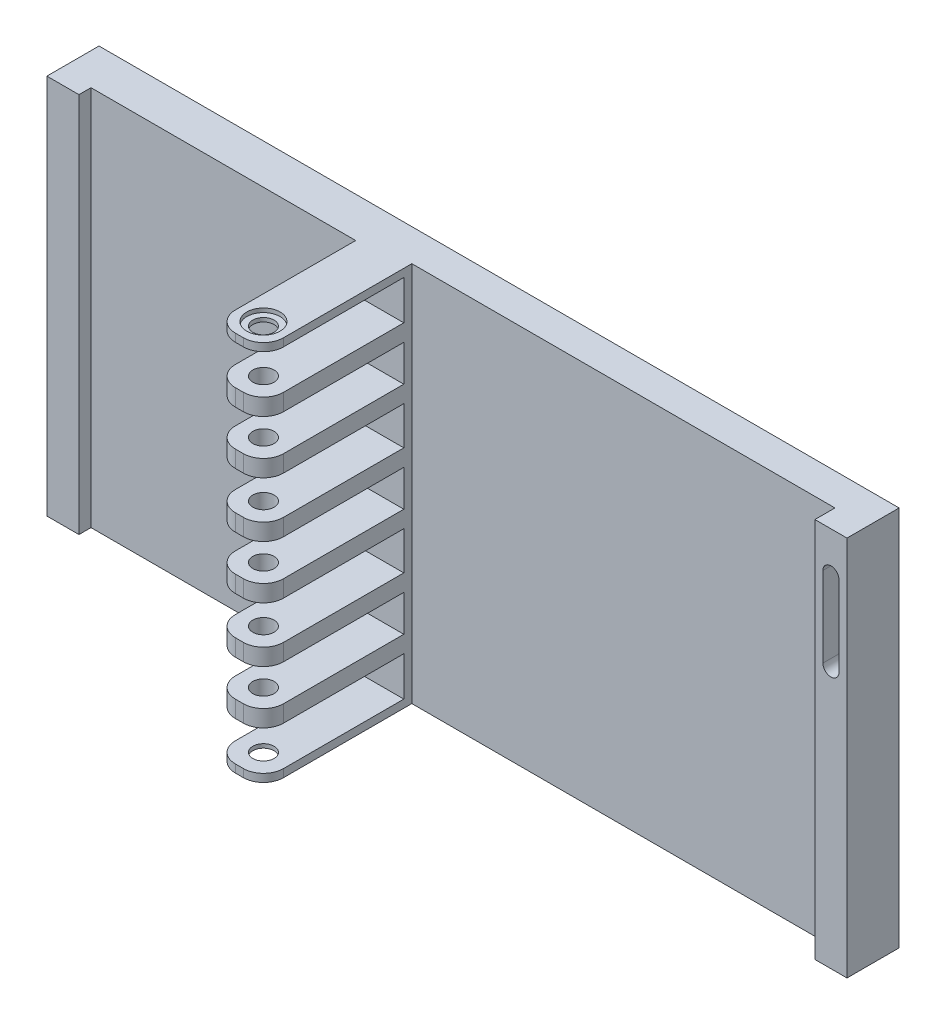
SolidWorks part; units mm, degrees
ref_plane "Front Plane" through (0, 0, 0) normal (1, 0, 0) x (0, 1, 0)
ref_plane "Top Plane" through (0, 0, 0) normal (0, 0, 1) x (0, 1, 0)
ref_plane "Right Plane" through (0, 0, 0) normal (0, 1, 0) x (-1, 0, 0)
sketch "Sketch1" plane through (0, 0, 0) normal (0, 0, 1) x (0, 1, 0)
  line L1 (0, 0) -> (-95, 0)
  line L2 (0, 0) -> (0, 12)
  line L3 (0, 12) -> (-95, 12)
  line L4 (-95, 0) -> (-95, 12)
extrude "Boss-Extrude1" add sketch "Sketch1" along normal blind 10 contours L3 L4 L1 L2
sketch "Sketch3" plane through (0, 0, 10) normal (0, 0, 1) x (1, 0, 0)
  line L0 (0, 0) -> (0, -95) construction
  line L1 (-12, 0) -> (0, 0)
  line L2 (-12, 0) -> (-12, -1.975)
  line L3 (-12, -1.975) -> (0, -1.975)
  line L4 (0, 0) -> (0, -1.975)
  line L6 (-12, -1.975) -> (0, -1.975) construction
  line L8 (-12, -11.775) -> (0, -11.775) construction
  line L10 (-12, -11.775) -> (0, -11.775)
  line L11 (-12, -11.775) -> (-12, -15.975)
  line L12 (-12, -15.975) -> (0, -15.975)
  line L13 (0, -11.775) -> (0, -15.975)
  line L14 (-12, -15.975) -> (0, -15.975) construction
  line L16 (-12, -25.025) -> (0, -25.025) construction
  line L18 (0, -25.025) -> (-12, -25.025)
  line L19 (0, -25.025) -> (0, -29.225)
  line L20 (0, -29.225) -> (-12, -29.225)
  line L21 (-12, -25.025) -> (-12, -29.225)
  line L23 (-12, -29.225) -> (0, -29.225) construction
  line L25 (-12, -38.775) -> (0, -38.775) construction
  line L27 (-12, -38.775) -> (0, -38.775)
  line L28 (-12, -38.775) -> (-12, -42.975)
  line L29 (-12, -42.975) -> (0, -42.975)
  line L30 (0, -38.775) -> (0, -42.975)
  dimension "D1" = 1.975
  dimension "D2" = 9.8
  dimension "D3" = 4.2
  dimension "D4" = 9.05
  dimension "D5" = 4.2
  dimension "D6" = 9.55
  dimension "D7" = 4.2
extrude "Boss-Extrude2" add sketch "Sketch3" along normal blind 35
fillet "Fillet1" radius 5 8 edges at (-12, -0.9875, 45) (0, -0.9875, 45) (-12, -13.875, 45) (0, -13.875, 45) (-12, -40.875, 45) (-12, -27.125, 45) (0, -27.125, 45) (0, -40.875, 45)
ref_plane "Plane1" through (0, -47.5, 0) normal (0, 1, 0) x (1, 0, 0)
mirror "Mirror1" about plane through (0, -47.5, 0) normal (0, 1, 0) of "Fillet1", "Boss-Extrude2"
sketch "Sketch5" plane through (0, 0, 0) normal (0, 1, 0) x (-1, 0, 0)
  line L0 (5, 45) -> (7, 45) construction
  line L1 (6, 45) -> (0, 45)
  line L2 (6, 45) -> (6, 39)
  line L3 (6, 39) -> (0, 39)
  line L4 (0, 45) -> (0, 39)
  circle A0 centre (6, 39) radius 2.65
  dimension "D1" = 6
extrude "Cut-Extrude1" cut sketch "Sketch5" against normal through all contours A0
sketch "Sketch7" plane through (0, 0, 0) normal (0, 1, 0) x (-1, 0, 0)
  line L0 (5, 45) -> (7, 45) construction
  line L1 (6, 45) -> (0, 45)
  line L2 (6, 45) -> (6, 39)
  line L3 (6, 39) -> (0, 39)
  line L4 (0, 45) -> (0, 39)
  line L5 (0, 40) -> (0, 0) construction
  circle A0 centre (6, 39) radius 4.15
  circle M6 centre (6, 39) radius 2.65
  dimension "D1" = 6
extrude "Cut-Extrude2" cut sketch "Sketch7" against normal blind 1 contours L3 A0 L2 M6 | L2 A0 L3 M6 region at (-8.8515, 0, 41.8515) region at (-3.8004, 0, 41.1996)
mirror "Mirror2" about plane through (0, -47.5, 0) normal (0, 1, 0) of "Cut-Extrude2"
sketch "Sketch8" plane through (0, 0, 0) normal (0, 0, -1) x (1, 0, 0)
  line L0 (0, 95) -> (-12, 95) construction
  line L1 (-6, 95) -> (-86, 95)
  line L2 (-6, 95) -> (-6, 0)
  line L3 (-6, 0) -> (-86, 0)
  line L4 (-86, 95) -> (-86, 0)
  line L5 (-6, 95) -> (113.5, 95)
  line L6 (-6, 95) -> (-6, 0)
  line L7 (-6, 0) -> (113.5, 0)
  line L8 (113.5, 95) -> (113.5, 0)
  line L9 (0, 0) -> (-12, 0) construction
  line M2 (0, 0) -> (0, 95)
  line M4 (-12, 95) -> (-12, 0)
  dimension "D1" = 119.5
  dimension "D2" = 80
extrude "Boss-Extrude3" add sketch "Sketch8" against normal blind 8 contours L1 L4 L3 M4 | L8 L5 L7 M2 region at (-49, -47.5, 0) region at (56.75, -47.5, 0)
sketch "Sketch9" plane through (0, 0, 8) normal (0, 0, 1) x (1, 0, 0)
  line L0 (0, -95) -> (113.5, -95) construction
  line L1 (113.5, 0) -> (105.5, 0)
  line L2 (113.5, 0) -> (113.5, -95)
  line L3 (113.5, -95) -> (105.5, -95)
  line L4 (105.5, 0) -> (105.5, -95)
  line L5 (-12, -95) -> (-86, -95) construction
  line L6 (-86, 0) -> (-78, 0)
  line L7 (-86, 0) -> (-86, -95)
  line L8 (-86, -95) -> (-78, -95)
  line L9 (-78, 0) -> (-78, -95)
  dimension "D1" = 8
extrude "Boss-Extrude4" add sketch "Sketch9" along normal blind 5
sketch "Sketch12" plane through (-12, 0, 0) normal (-1, 0, 0) x (0, -1, 0)
  line L0 (95, 40) -> (95, 8) construction
  line L1 (0, 8) -> (95, 8)
  line L2 (0, 8) -> (0, 10)
  line L3 (0, 10) -> (95, 10)
  line L4 (95, 8) -> (95, 10)
sketch "Sketch11" plane through (0, 0, 13) normal (0, 0, 1) x (1, 0, 0)
  line L0 (109.5, 0) -> (109.5, -95) construction
  line L1 (113.5, 0) -> (105.5, 0) construction
  line L2 (105.5, -95) -> (113.5, -95) construction
  line L3 (109.5, -10) -> (109.5, -30) construction
  line L4 (111.5, -10) -> (111.5, -30)
  line L5 (107.5, -10) -> (107.5, -30)
  line L7 (113.5, 0) -> (109.5, 0)
  line L8 (113.5, 0) -> (113.5, -10)
  line L9 (113.5, -10) -> (109.5, -10)
  line L10 (109.5, 0) -> (109.5, -10)
  arc A0 (111.5, -10) -> (107.5, -10) centre (109.5, -10) ccw
  arc A1 (107.5, -30) -> (111.5, -30) centre (109.5, -30) ccw
  point P8 (109.5, -20)
  dimension "D1" = 10
  dimension "D2" = 20
extrude "Cut-Extrude3" cut sketch "Sketch11" against normal blind 10 contours L4 A1 L5 A0
pattern_linear "LPattern1" [suppressed] count 2 spacing 55 of bodies 112
extrude "Boss-Extrude5" add sketch "Sketch12" along normal up to next
equation "\"whitekey_cutout_length\"= 101.5"
equation "\"mount_recess_length\"=50"
equation "\"mount_recess_height\"=12.5"
equation "\"mount_recess_depth\"=1.5"
equation "\"wall_thickness\"=8"
equation "\"D1@Sketch9\"=\"wall_thickness\""
equation "\"D2@Sketch9\"=\"wall_thickness\""
equation "\"D1@Boss-Extrude3\"=\"wall_thickness\""
equation "\"base_mount_height\"=35"
equation "\"D1@Boss-Extrude2\"=\"base_mount_height\""
equation "\"base_rear_length\"=80"
equation "\"D1@Sketch8\"=\"wall_thickness\"+110+1.5"
equation "\"D2@Sketch8\"=\"base_rear_length\""
